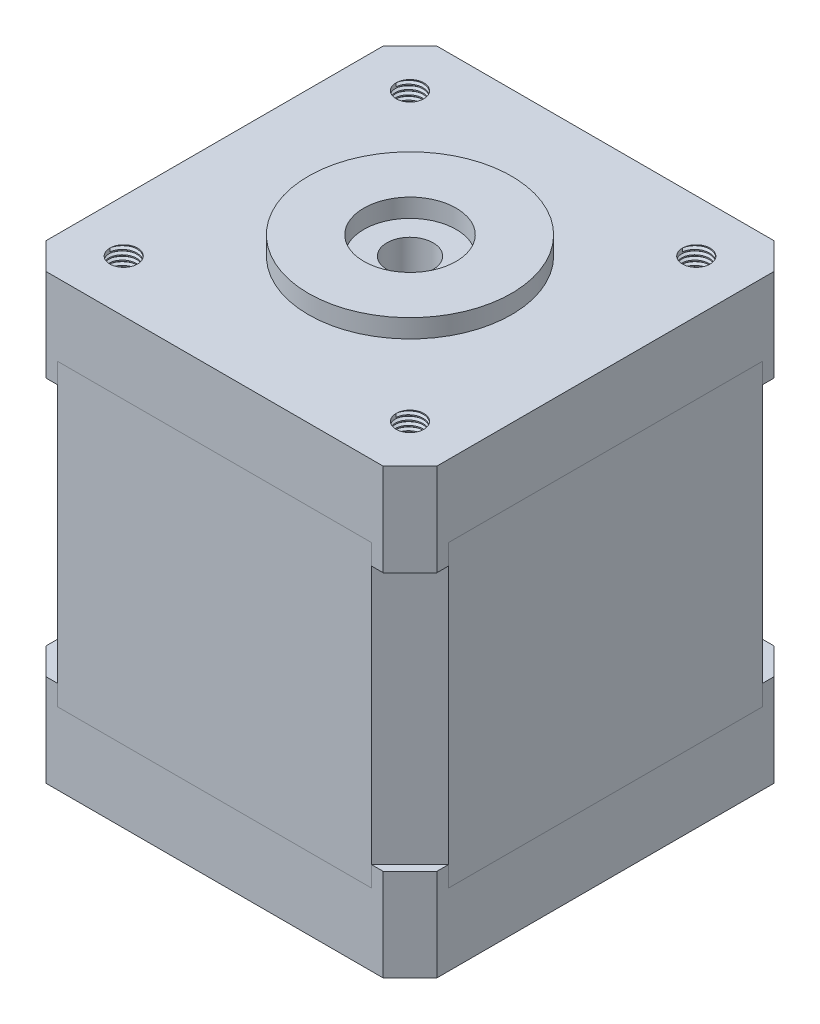
SolidWorks part; units mm, degrees
ref_plane "Front Plane" through (0, 0, 0) normal (0, 0, 1) x (1, 0, 0)
ref_plane "Top Plane" through (0, 0, 0) normal (0, 1, 0) x (1, 0, 0)
ref_plane "Right Plane" through (0, 0, 0) normal (1, 0, 0) x (0, 0, -1)
sketch "Sketch1" plane through (0, 0, 0) normal (0, 1, 0) x (1, 0, 0)
  line L0 (-21.15, 18.25) -> (-18.25, 21.15)
  line L1 (-21.15, -21.15) -> (21.15, -21.15) construction
  line L2 (-21.15, -21.15) -> (-21.15, 21.15) construction
  line L3 (-21.15, 21.15) -> (21.15, 21.15) construction
  line L4 (21.15, -21.15) -> (21.15, 21.15) construction
  line L5 (-21.15, -21.15) -> (21.15, 21.15) construction
  line L6 (-21.15, 21.15) -> (21.15, -21.15) construction
  line L7 (-18.25, 21.15) -> (18.25, 21.15)
  line L8 (0, 21.15) -> (0, 0) construction
  line L9 (0, 0) -> (21.15, 0) construction
  line L10 (21.15, 18.25) -> (18.25, 21.15)
  line L11 (21.15, -18.25) -> (18.25, -21.15)
  line L12 (-18.25, -21.15) -> (18.25, -21.15)
  line L13 (-21.15, -18.25) -> (-18.25, -21.15)
  line L14 (-21.15, 18.25) -> (-21.15, -18.25)
  line L15 (21.15, 18.25) -> (21.15, -18.25)
  point P0 (0, 0)
  dimension "D1" = 42.3
  dimension "D2" = 2.9
  dimension "D3" = 2.9
  dimension "D4" = 36.5
extrude "Boss-Extrude1" add sketch "Sketch1" along normal blind 10
sketch "Sketch2" plane through (0, 10, 0) normal (0, 1, 0) x (1, 0, 0)
  line L0 (18.25, 21.15) -> (-18.25, 21.15) construction
  line L1 (-17, -21.15) -> (17, -21.15)
  line L2 (-17, -21.15) -> (-17, -17) construction
  line L3 (-17, 21.15) -> (17, 21.15)
  line L4 (17, -17) -> (17, -13.6643) construction
  line L5 (-17, -21.15) -> (-13.6643, -17) construction
  line L6 (0, 0) -> (17, -21.15) construction
  line L7 (21.15, -18.25) -> (21.15, 18.25) construction
  line L8 (17, -17) -> (21.15, -17) construction
  line L9 (-21.15, -17) -> (-21.15, 17)
  line L10 (-21.15, 17) -> (-17, 17) construction
  line L11 (21.15, -17) -> (21.15, 17)
  line L12 (-21.15, -17) -> (-17, -13.6643) construction
  line L13 (-21.15, 17) -> (-17, 13.6643) construction
  line L14 (-21.15, 17) -> (-17, 21.15)
  line L15 (17, 21.15) -> (21.15, 17)
  line L16 (-21.15, -17) -> (-17, -21.15)
  line L17 (17, -21.15) -> (21.15, -17)
  line L18 (-17, -13.6643) -> (-17, 13.6643) construction
  line L19 (-17, 17) -> (-17, 21.15) construction
  line L20 (-17, 13.6643) -> (0, 0) construction
  line L21 (0, 0) -> (17, -13.6643) construction
  line L22 (-17, 17) -> (-13.6643, 17) construction
  line L23 (13.6643, 17) -> (17, 17) construction
  line L24 (-17, 21.15) -> (-13.6643, 17) construction
  line L25 (-17, 13.6643) -> (-17, 17) construction
  line L26 (-13.6643, 17) -> (0, 0) construction
  line L27 (-13.6643, 17) -> (13.6643, 17) construction
  line L28 (-17, -13.6643) -> (0, 0) construction
  line L29 (0, 0) -> (21.15, 17) construction
  line L30 (-17, -17) -> (-17, -13.6643) construction
  line L31 (-21.15, -17) -> (-17, -17) construction
  line L32 (-17, -17) -> (-13.6643, -17) construction
  line L33 (-13.6643, -17) -> (0, 0) construction
  line L34 (0, 0) -> (17, 21.15) construction
  line L35 (-13.6643, -17) -> (13.6643, -17) construction
  line L36 (13.6643, -17) -> (17, -17) construction
  line L37 (17, -21.15) -> (17, -17) construction
  line L38 (17, -13.6643) -> (21.15, -17) construction
  line L39 (17, -13.6643) -> (17, 13.6643) construction
  line L40 (17, 17) -> (17, 21.15) construction
  line L41 (17, 13.6643) -> (17, 17) construction
  line L42 (17, 17) -> (21.15, 17) construction
  point P0 (0, 0)
  point P8 (0, 0)
  dimension "D1" = 34
  dimension "D2" = 34
extrude "Cut-Extrude1" cut sketch "Sketch2" against normal blind 2.2
sketch "Sketch3" plane through (0, 7.8, 0) normal (0, 1, 0) x (1, 0, 0)
  line L8 (21.15, 17) -> (17, 21.15)
  line L9 (17, 21.15) -> (-17, 21.15)
  line L10 (-17, 21.15) -> (-21.15, 17)
  line L11 (-21.15, 17) -> (-21.15, -17)
  line L12 (-21.15, -17) -> (-17, -21.15)
  line L13 (-17, -21.15) -> (17, -21.15)
  line L14 (17, -21.15) -> (21.15, -17)
  line L15 (21.15, -17) -> (21.15, 17)
  line L16 (21.15, 17) -> (17, 21.15)
  line L17 (17, 21.15) -> (-17, 21.15)
  line L18 (-17, 21.15) -> (-21.15, 17)
  line L19 (-21.15, 17) -> (-21.15, -17)
  line L20 (-21.15, -17) -> (-17, -21.15)
  line L21 (-17, -21.15) -> (17, -21.15)
  line L22 (17, -21.15) -> (21.15, -17)
  line L23 (21.15, -17) -> (21.15, 17)
  dimension "D1" = 0
ref_plane "Plane1" through (0, 48, 0) normal (0, -1, 0) x (-1, 0, 0)
sketch "Sketch6" plane through (0, 48, 0) normal (0, -1, 0) x (-1, 0, 0)
  line L8 (21.15, -18.25) -> (21.15, 18.25)
  line L9 (21.15, 18.25) -> (18.25, 21.15)
  line L10 (18.25, 21.15) -> (-18.25, 21.15)
  line L11 (-18.25, 21.15) -> (-21.15, 18.25)
  line L12 (-21.15, 18.25) -> (-21.15, -18.25)
  line L13 (-21.15, -18.25) -> (-18.25, -21.15)
  line L14 (-18.25, -21.15) -> (18.25, -21.15)
  line L15 (18.25, -21.15) -> (21.15, -18.25)
  line L16 (21.15, -18.25) -> (21.15, 18.25)
  line L17 (21.15, 18.25) -> (18.25, 21.15)
  line L18 (18.25, 21.15) -> (-18.25, 21.15)
  line L19 (-18.25, 21.15) -> (-21.15, 18.25)
  line L20 (-21.15, 18.25) -> (-21.15, -18.25)
  line L21 (-21.15, -18.25) -> (-18.25, -21.15)
  line L22 (-18.25, -21.15) -> (18.25, -21.15)
  line L23 (18.25, -21.15) -> (21.15, -18.25)
  dimension "D1" = 0
extrude "Boss-Extrude4" add sketch "Sketch6" along normal blind 10 separate body
sketch "Sketch7" plane through (0, 38, 0) normal (0, -1, 0) x (1, 0, 0)
  line L8 (17, -21.15) -> (21.15, -17)
  line L9 (-17, -21.15) -> (17, -21.15)
  line L10 (-21.15, -17) -> (-17, -21.15)
  line L11 (-21.15, 17) -> (-21.15, -17)
  line L12 (-17, 21.15) -> (-21.15, 17)
  line L13 (17, 21.15) -> (-17, 21.15)
  line L14 (21.15, 17) -> (17, 21.15)
  line L15 (21.15, -17) -> (21.15, 17)
  line L16 (17, -21.15) -> (21.15, -17)
  line L17 (-17, -21.15) -> (17, -21.15)
  line L18 (-21.15, -17) -> (-17, -21.15)
  line L19 (-21.15, 17) -> (-21.15, -17)
  line L20 (-17, 21.15) -> (-21.15, 17)
  line L21 (17, 21.15) -> (-17, 21.15)
  line L22 (21.15, 17) -> (17, 21.15)
  line L23 (21.15, -17) -> (21.15, 17)
  dimension "D1" = 0
extrude "Cut-Extrude2" cut sketch "Sketch7" against normal blind 2.2
extrude "Boss-Extrude5" add sketch "Sketch2<2>" along normal blind 30.2 and the other way blind 2.2 separate body
sketch "Sketch2<2>" plane through (0, 10, 0) normal (0, 1, 0) x (1, 0, 0) same geometry as "Sketch2"
sketch "Sketch8" plane through (0, 48, 0) normal (0, 1, 0) x (1, 0, 0)
  circle A0 centre (0, 0) radius 10.9982
  dimension "D1" = 21.9964
extrude "Boss-Extrude6" add sketch "Sketch8" along normal blind 2
sketch "Sketch9" plane through (0, 50, 0) normal (0, 1, 0) x (1, 0, 0)
  circle A0 centre (0, 0) radius 2.5
  dimension "D1" = 5
extrude "Cut-Extrude3" cut sketch "Sketch9" against normal up to surface (50 mm away) up to face at (0, 0, 0)
sketch "Sketch10" plane through (0, 50, 0) normal (0, 1, 0) x (1, 0, 0)
  circle A0 centre (0, 0) radius 5
  dimension "D1" = 10
extrude "Cut-Extrude4" cut sketch "Sketch10" against normal blind 2
ref_plane "Plane2" through (0, 24, 0) normal (0, -1, 0) x (-1, 0, 0)
sketch "Sketch11" plane through (0, 0, 0) normal (0, -1, 0) x (1, 0, 0)
  circle A0 centre (0, 0) radius 5
  dimension "D1" = 10
extrude "Cut-Extrude5" cut sketch "Sketch11" against normal blind 2
sketch "Sketch12" plane through (0, 48, 0) normal (0, 1, 0) x (1, 0, 0)
  line L1 (15.5, -15.5) -> (-15.5, -15.5) construction
  line L2 (15.5, -15.5) -> (15.5, 15.5) construction
  line L3 (15.5, 15.5) -> (-15.5, 15.5) construction
  line L4 (-15.5, -15.5) -> (-15.5, 15.5) construction
  line L5 (15.5, -15.5) -> (-15.5, 15.5) construction
  line L6 (15.5, 15.5) -> (-15.5, -15.5) construction
  circle A0 centre (-15.5, 15.5) radius 1.5
  circle A1 centre (15.5, 15.5) radius 1.5
  circle A2 centre (15.5, -15.5) radius 1.5
  circle A3 centre (-15.5, -15.5) radius 1.5
  point P2 (0, 0)
  dimension "D1" = 31
  dimension "D2" = 3
extrude "Cut-Extrude6" cut sketch "Sketch12" against normal blind 4.5
thread "Thread1" pitch 0.5 method cut profile "Thread Profile1" start angle 0, offset 0, length 4.5, pitch 0.5, diameter 3
ref_plane "Plane3" through (-17, 48, -15.5) normal (0, 0, 1) x (-1, 0, 0)
sketch "Thread Profile1" plane through (-17, 48, -15.5) normal (0, 0, 1) x (-1, 0, 0)
  line L0 (0, 0) -> (0, 0.5) construction
  line L1 (0, 0) -> (0.2706, 0.1562)
  line L2 (0.2706, 0.1562) -> (0.2706, 0.2187)
  line L3 (0.2706, 0.2187) -> (0, 0.375)
  line L4 (0.2706, 0.1875) -> (0, 0.1875) construction
  line L11 (0, 0) -> (0, 0.375)
  point P2 (0, 0)
  dimension "Pitch" = 0.5
  dimension "Profile_Angle" = 60
  dimension "Profile_Land" = 0.0625
  dimension "Profile_Height" = 0.2706
pattern_linear "LPattern1" count 2 spacing 31 along (1, 0, 0) count 2 spacing 31 along (0, 0, 1) of "Thread1"
ref_axis "Axis1" through (0, 40.2, 0) along (0, 1, 0)
sketch "Sketch13" plane through (0, 0, 0) normal (0, -1, 0) x (1, 0, 0)
  line L1 (15.5, -15.5) -> (-15.5, -15.5) construction
  line L2 (15.5, -15.5) -> (15.5, 15.5) construction
  line L3 (15.5, 15.5) -> (-15.5, 15.5) construction
  line L4 (-15.5, -15.5) -> (-15.5, 15.5) construction
  line L5 (15.5, -15.5) -> (-15.5, 15.5) construction
  line L6 (15.5, 15.5) -> (-15.5, -15.5) construction
  circle A0 centre (-15.5, 15.5) radius 1.5
  circle A1 centre (15.5, 15.5) radius 1.5
  circle A2 centre (15.5, -15.5) radius 1.5
  circle A3 centre (-15.5, -15.5) radius 1.5
  point P2 (0, 0)
  dimension "D2" = 3
  dimension "D1" = 31
extrude "Cut-Extrude7" cut sketch "Sketch13" against normal blind 4.5
chamfer "Chamfer1" distance 0.5 angle 45 4 edges at (15.5, 0, 14) (-15.5, 0, 14) (-15.5, 0, -17) (15.5, 0, -17)
